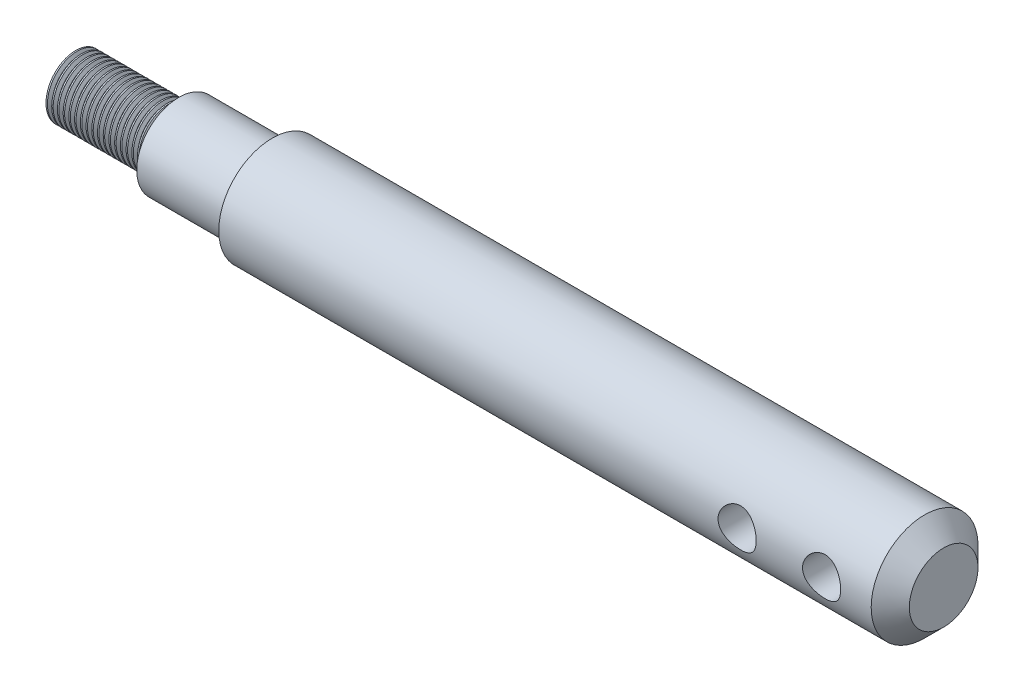
SolidWorks part; units mm, degrees
ref_plane "Front Plane" through (0, 0, 0) normal (0, 0, 1) x (1, 0, 0)
ref_plane "Top Plane" through (0, 0, 0) normal (0, 1, 0) x (1, 0, 0)
ref_plane "Right Plane" through (0, 0, 0) normal (1, 0, 0) x (0, 0, -1)
sketch "Sketch2" plane through (0, 0, 0) normal (0, 0, 1) x (1, 0, 0)
  line L0 (0, 0) -> (228, 0)
  line L1 (228, 0) -> (228, 9)
  line L2 (223, 14) -> (52, 14)
  line L3 (52, 14) -> (52, 11)
  line L4 (52, 11) -> (27.5, 11)
  line L5 (27.5, 11) -> (27.5, 7.13)
  line L6 (27.5, 7.13) -> (0, 7.13)
  line L7 (0, 7.13) -> (0, 0)
  line L8 (228, 9) -> (223, 14)
  point P4 (228, 14)
  dimension "D1" = 228
  dimension "D2" = 14
  dimension "D3" = 11
  dimension "D4" = 7.13
  dimension "D5" = 27.5
  dimension "D6" = 24.5
revolve "Revolve1" add sketch "Sketch2" angle 360 about L0
ref_plane "Plane1" through (0, 0, 20) normal (0, 0, 1) x (1, 0, 0)
hole_wizard "Ø10.0 (10) Diameter Hole1" positions "Sketch3" profile "Sketch4" hole size "Ø10.0" standard "ISO" end condition through all
sketch "Sketch3" plane through (0, 0, 20) normal (0, 0, 1) x (1, 0, 0)
  line L0 (228, -9) -> (228, 9) construction
  point P0 (210, 0)
  point P2 (187.86, 0)
  dimension "D1" = 18
  dimension "D2" = 40.14
sketch "Sketch4" plane through (210, 0, 20) normal (1, 0, 0) x (0, -1, 0)
  line L0 (0, 0) -> (0, 34)
  line L1 (0, 34) -> (5, 34)
  line L2 (5, 34) -> (5, 0)
  line L5 (5, 0) -> (0, 0)
  line L11 (0, -6.35) -> (0, 107.95) construction
  dimension "Thru Hole Dia." = 10
  dimension "Thru Hole Depth" = 34
thread "Thread1" pitch 1.5 method extrude profile "Thread Profile1" start angle 0, offset 1, length 0, pitch 1.5, diameter 14.26
ref_plane "Plane2" through (28.5, 0, 7.13) normal (0, 1, 0) x (0, 0, -1)
sketch "Thread Profile1" plane through (28.5, 0, 7.13) normal (0, 1, 0) x (0, 0, -1)
  line L0 (0, 0) -> (0, 1.5) construction
  line L11 (0, 0) -> (0, 1.3125)
  line L12 (0, 1.3125) -> (-0.8119, 0.8437)
  line L13 (-0.8119, 0.8437) -> (-0.8119, 0.4687)
  line L15 (-0.8119, 0.4687) -> (0, 0)
  line L17 (-0.8119, 0.6562) -> (0, 0.6562) construction
  point P2 (0, 0)
  dimension "Pitch" = 1.5
  dimension "Profile_Angle" = 60
  dimension "Profile_Land" = 0.375
  dimension "Profile_Height" = 0.8119
other "SurfaceCut1"
